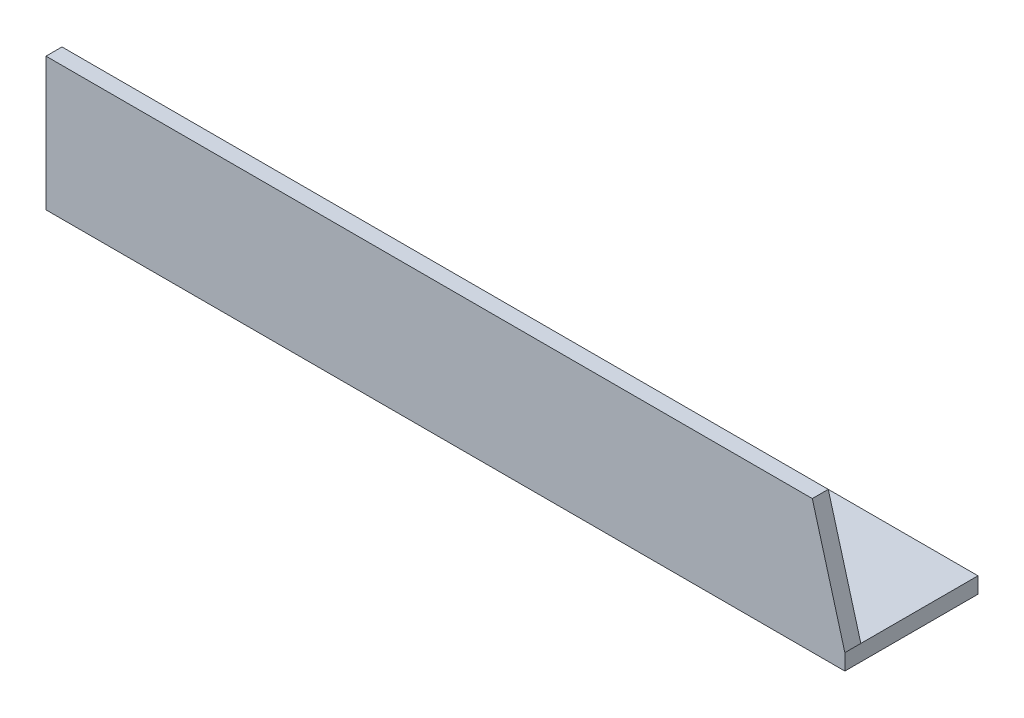
SolidWorks part; units mm, degrees
ref_plane "Спереди" through (0, 0, 0) normal (0, 0, 1) x (1, 0, 0)
ref_plane "Сверху" through (0, 0, 0) normal (0, 1, 0) x (1, 0, 0)
ref_plane "Справа" through (0, 0, 0) normal (1, 0, 0) x (0, 0, -1)
sketch "Эскиз1" plane through (0, 0, 0) normal (1, 0, 0) x (0, 0, -1)
  line L0 (0, 50) -> (0, 0)
  line L1 (0, 0) -> (50, 0)
extrude "Вытянуть-Тонкостенный1" add sketch "Эскиз1" along normal blind 300 thin thin type one direction reverse wall 6
sketch "Эскиз2" plane through (0, 0, 0) normal (0, 0, 1) x (1, 0, 0)
  line L0 (287.7735, 50) -> (300, 50)
  line L1 (300, 50) -> (0, 50) construction
  line L2 (300, 50) -> (300, 6)
  line L3 (0, 6) -> (300, 6) construction
  line L4 (300, 50) -> (300, 0) construction
  line L5 (300, 6) -> (287.7735, 50)
extrude "Вырез-Вытянуть1" cut sketch "Эскиз2" against normal through all
